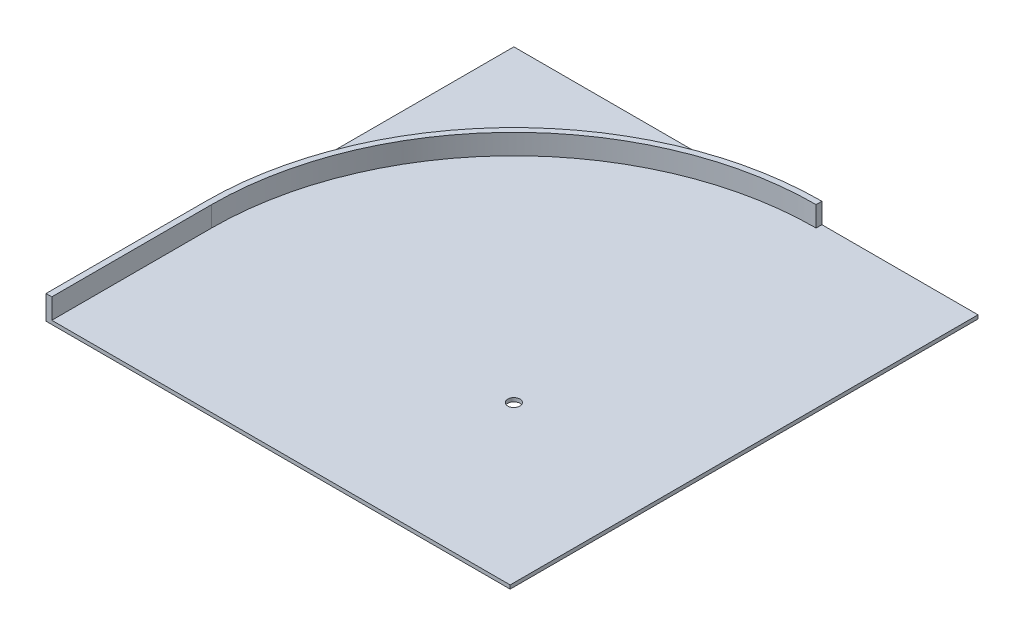
SolidWorks part; units mm, degrees
ref_plane "Front Plane" through (0, 0, 0) normal (0, 0, 1) x (1, 0, 0)
ref_plane "Top Plane" through (0, 0, 0) normal (0, 1, 0) x (1, 0, 0)
ref_plane "Right Plane" through (0, 0, 0) normal (1, 0, 0) x (0, 0, -1)
sketch "Sketch3" plane through (0, 0, 0) normal (0, 1, 0) x (1, 0, 0)
  line L0 (0, 521) -> (0, 531)
  line L1 (0, 0) -> (-839.8654, 0) construction
  line L2 (0, 0) -> (-451.1992, 260.5) construction
  line L5 (-521, 0) -> (-531, 0)
  circle A0 centre (0, 0) radius 250 construction
  arc A3 (0, 521) -> (-521, 0) centre (0, 0) ccw
  arc A4 (0, 531) -> (-531, 0) centre (0, 0) ccw
  dimension "D1" = 521
  dimension "D2" = 10
  dimension "D3" = 30
extrude "Boss-Extrude1" add sketch "Sketch3" along normal blind 35
sketch "Sketch4" plane through (0, 0, 0) normal (0, 1, 0) x (1, 0, 0)
  line L1 (-531, -275.4) -> (269, -275.4)
  line L2 (-531, -275.4) -> (-531, 531)
  line L3 (-531, 531) -> (269, 531)
  line L4 (269, -275.4) -> (269, 531)
  dimension "D1" = 800
  dimension "D2" = 275.4
extrude "Boss-Extrude2" add sketch "Sketch4" against normal blind 6.35
hole_wizard "Ø20.0mm Dowel Hole1" positions "Sketch6" profile "Sketch7" hole size "Ø20.0" standard "ANSI Metric" end condition through all
sketch "Sketch6" plane through (0, 0, 0) normal (0, 1, 0) x (1, 0, 0)
  point P0 (0, 0)
sketch "Sketch7" plane through (0, 0, 0) normal (1, 0, 0) x (0, 0, 1)
  line L0 (0, 0) -> (0, 6.35)
  line L1 (0, 6.35) -> (10.5, 6.35)
  line L2 (10.5, 6.35) -> (10.5, 0)
  line L5 (10.5, 0) -> (0, 0)
  line L11 (0, -6.35) -> (0, 107.95) construction
  dimension "Thru Hole Dia." = 21
  dimension "Thru Hole Depth" = 6.35
sketch "Sketch8" plane through (0, 0, 0) normal (0, 0, 1) x (1, 0, 0)
  line L1 (-531, 35) -> (-521, 35)
  line L2 (-531, 35) -> (-531, 0)
  line L3 (-531, 0) -> (-521, 0)
  line L4 (-521, 35) -> (-521, 0)
extrude "Boss-Extrude3" add sketch "Sketch8" along normal up to surface (275.4 mm away) up to face at (-131, -3.175, 275.4)
